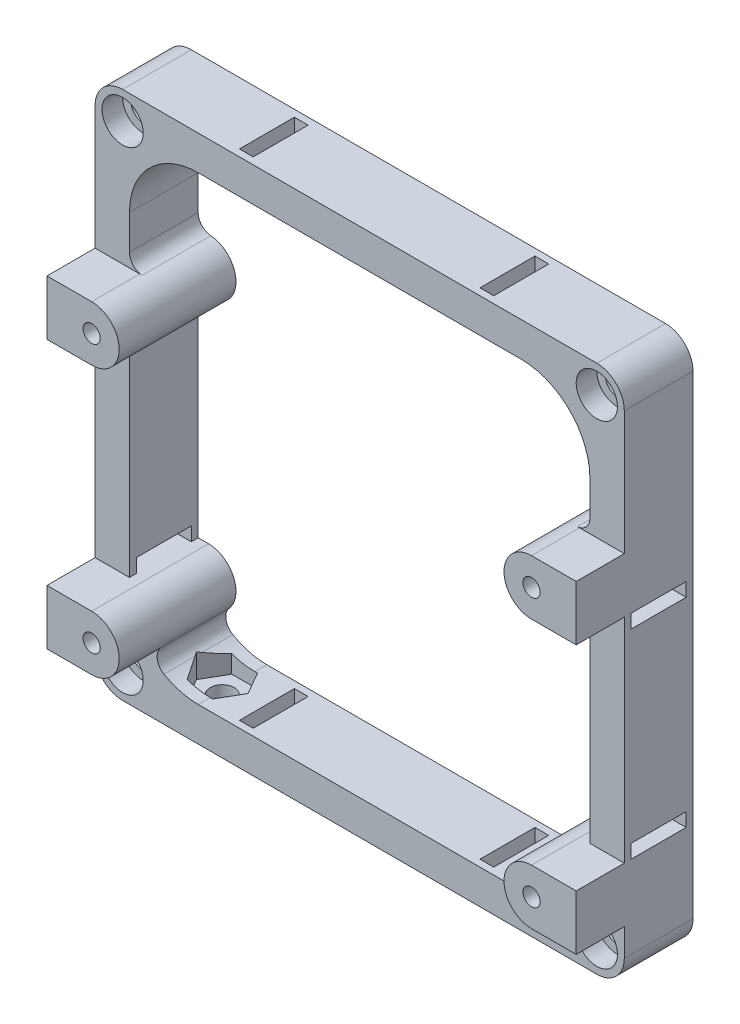
SolidWorks part; units mm, degrees
ref_plane "Front Plane" through (0, 0, 0) normal (0, 0, 1) x (1, 0, 0)
ref_plane "Top Plane" through (0, 0, 0) normal (0, 1, 0) x (1, 0, 0)
ref_plane "Right Plane" through (0, 0, 0) normal (1, 0, 0) x (0, 0, -1)
sketch "Sketch1" plane through (0, 0, 0) normal (0, 0, 1) x (1, 0, 0)
  line L1 (-38.5, -38.5) -> (38.5, -38.5)
  line L2 (-38.5, -38.5) -> (-38.5, 38.5)
  line L3 (-38.5, 38.5) -> (38.5, 38.5)
  line L4 (38.5, -38.5) -> (38.5, 38.5)
  line L5 (-38.5, -38.5) -> (38.5, 38.5) construction
  line L6 (-38.5, 38.5) -> (38.5, -38.5) construction
  point P0 (0, 0)
  dimension "D1" = 77
  dimension "D2" = 77
extrude "Extrude-Thin1" add sketch "Sketch1" along normal blind 10 thin thin type one direction reverse wall 5
fillet "Fillet2" radius 10 4 edges at (33.5, 33.5, 5) (33.5, -33.5, 5) (-33.5, -33.5, 5) (-33.5, 33.5, 5)
fillet "Fillet1" radius 4 4 edges at (38.5, -38.5, 5) (-38.5, -38.5, 5) (38.5, 38.5, 5) (-38.5, 38.5, 5)
sketch "Sketch2" plane through (0, 0, 10) normal (0, 0, 1) x (1, 0, 0)
  line L0 (-38.5, 34.5) -> (-38.5, -34.5) construction
  line L1 (34.5, 38.5) -> (-34.5, 38.5) construction
  circle A0 centre (-34.5, 34.5) radius 1.75
  dimension "D1" = 3.5
  dimension "D2" = 4
  dimension "D3" = 4
extrude "Cut-Extrude1" cut sketch "Sketch2" against normal through all
sketch "Sketch3" plane through (0, 0, 10) normal (0, 0, 1) x (1, 0, 0)
  circle A0 centre (-34.5, 34.5) radius 3
  dimension "D1" = 6
extrude "Cut-Extrude2" cut sketch "Sketch3" against normal offset from surface (3 mm away) 7 up to face at (-32.75, 34.5, 0)
mirror "Mirror1" about plane through (0, 0, 0) normal (1, 0, 0) of "Cut-Extrude2", "Cut-Extrude1"
mirror "Mirror2" about plane through (0, 0, 0) normal (0, 1, 0) of "Mirror1"
sketch "Sketch4" plane through (0, 0, 0) normal (0, 0, 1) x (1, 0, 0)
  line L1 (38.5, -34.5) -> (38.5, 34.5) construction
  line L2 (38.5, -30.5) -> (32, -30.5)
  line L3 (38.5, -30.5) -> (38.5, -22.5)
  line L4 (38.5, -22.5) -> (32, -22.5)
  line L7 (-34.5, -38.5) -> (34.5, -38.5) construction
  arc A0 (32, -22.5) -> (32, -30.5) centre (32, -26.5) ccw
  dimension "D1" = 32
  dimension "D2" = 8
  dimension "D3" = 12
extrude "Boss-Extrude2" add sketch "Sketch4" along normal blind 17
sketch "Sketch5" plane through (0, 0, 17) normal (0, 0, 1) x (1, 0, 0)
  line L0 (38.5, -26.5) -> (32, -26.5) construction
  line L1 (38.5, -30.5) -> (38.5, -22.5) construction
  circle A0 centre (32, -26.5) radius 1.25
  dimension "D2" = 2.5
  dimension "D1" = 32
extrude "Cut-Extrude3" cut sketch "Sketch5" against normal blind 8
pattern_linear "LPattern1" count 2 spacing 39 along (0, 1, 0) of "Boss-Extrude2", "Cut-Extrude3"
mirror "Mirror3" about plane through (0, 0, 0) normal (1, 0, 0) of "LPattern1"
sketch "Sketch9" plane through (0, -38.5, 0) normal (0, -1, 0) x (1, 0, 0)
  line L0 (-34.5, 0) -> (34.5, 0) construction
  circle A0 centre (-25, 5) radius 1.75
  point P2 (0, 0)
  dimension "D3" = 3.5
  dimension "D1" = 25
  dimension "D2" = 5
extrude "Cut-Extrude6" cut sketch "Sketch9" against normal up to next
sketch "Sketch10" plane through (0, -38.5, 0) normal (0, -1, 0) x (1, 0, 0)
  line L1 (-21.2472, 5) -> (-23.1236, 8.25)
  line L2 (-23.1236, 8.25) -> (-26.8764, 8.25)
  line L3 (-26.8764, 8.25) -> (-28.7528, 5)
  line L4 (-28.7528, 5) -> (-26.8764, 1.75)
  line L5 (-26.8764, 1.75) -> (-23.1236, 1.75)
  line L6 (-23.1236, 1.75) -> (-21.2472, 5)
  circle A0 centre (-25, 5) radius 3.25 construction
  dimension "D1" = 6.5
extrude "Cut-Extrude7" cut sketch "Sketch10" against normal up to next from offset 3 offset against normal yes
mirror "Mirror4" about plane through (0, 0, 0) normal (1, 0, 0) of "Cut-Extrude7", "Cut-Extrude6"
sketch "Sketch11" plane through (0, 0, 0) normal (0, 0, 1) x (1, 0, 0)
  line L0 (-33.5, 8.5) -> (-33.5, -22.5) construction
  line L1 (-38.5, 8.5) -> (-33.5, 8.5)
  line L2 (-38.5, 8.5) -> (-38.5, 6.5)
  line L3 (-38.5, 6.5) -> (-33.5, 6.5)
  line L4 (-33.5, 8.5) -> (-33.5, 6.5)
  dimension "D1" = 2
extrude "Cut-Extrude8" cut sketch "Sketch11" along normal offset from surface (8 mm away) 1 from offset 1 up to face at (-36, -7, 10)
pattern_linear "LPattern2" count 2 along (0, -1, 0) of "Cut-Extrude8"
mirror "Mirror5" about plane through (0, 0, 0) normal (1, 0, 0) of "LPattern2"
sketch "Sketch12" plane through (0, 0, 0) normal (0, 0, 1) x (1, 0, 0)
  line L0 (34.5, 38.5) -> (-34.5, 38.5) construction
  line L1 (-18.5, 38.5) -> (-16.5, 38.5)
  line L2 (-18.5, 38.5) -> (-18.5, -38.5)
  line L3 (-18.5, -38.5) -> (-16.5, -38.5)
  line L4 (-16.5, 38.5) -> (-16.5, -38.5)
  line L5 (-34.5, -38.5) -> (34.5, -38.5) construction
  line L6 (-38.5, 34.5) -> (-38.5, 16.5) construction
  dimension "D1" = 2
  dimension "D2" = 20
extrude "Cut-Extrude9" cut sketch "Sketch12" along normal offset from surface (8 mm away) 1 from offset 1 up to face at (0, 27.6499, 10)
fillet "Fillet3" radius 2 2 edges at (-30.8135, -30.32, 5) (30.8135, -30.32, 5)
fillet "Fillet4" radius 2 2 edges at (33.5, 16.5, 5) (-33.5, 16.5, 5)
mirror "Mirror6" about plane through (0, 0, 0) normal (1, 0, 0) of "Cut-Extrude9"
